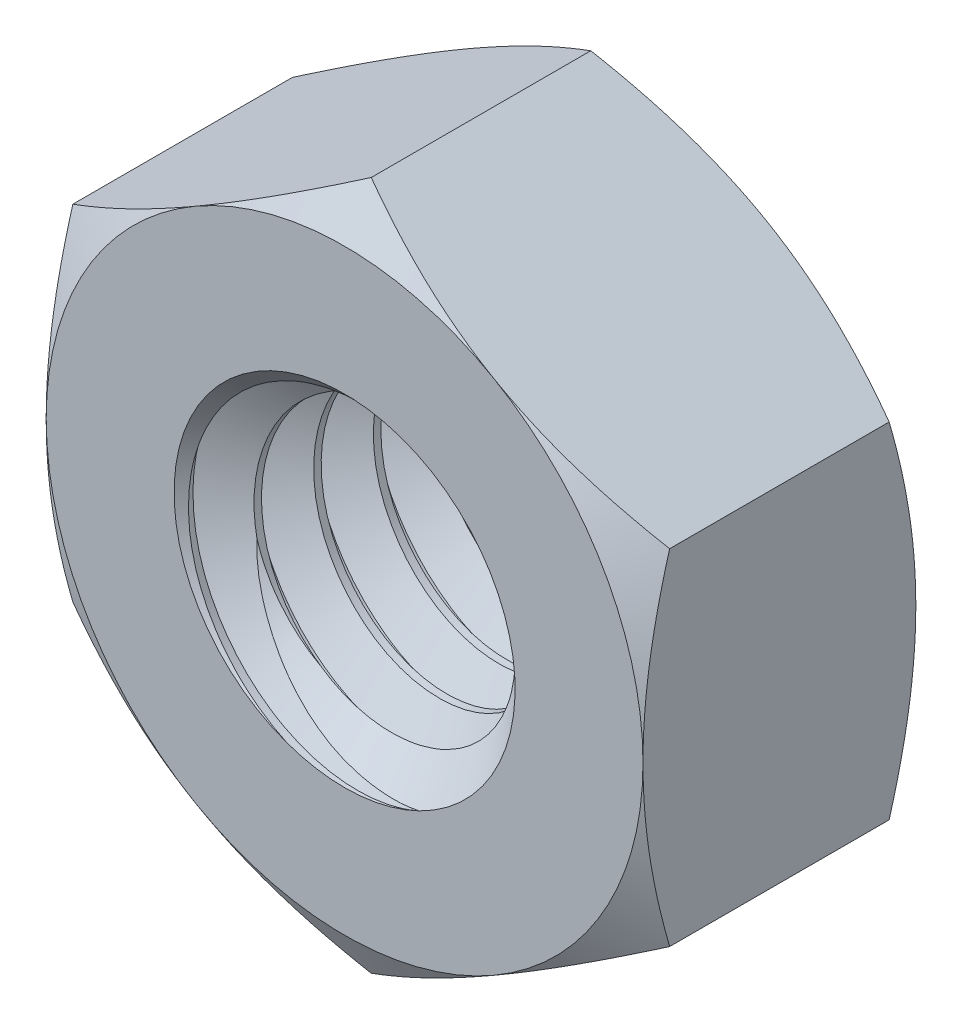
SolidWorks part; units mm, degrees
ref_plane "Front" through (0, 0, 0) normal (0, 0, 1) x (1, 0, 0)
ref_plane "Top" through (0, 0, 0) normal (0, 1, 0) x (1, 0, 0)
ref_plane "Right" through (0, 0, 0) normal (1, 0, 0) x (0, 0, -1)
sketch "Sketch1" plane through (0, 0, 0) normal (0, 0, 1) x (1, 0, 0)
  line L1 (-3.5, 2.0207) -> (-3.5, -2.0207)
  line L2 (-3.5, -2.0207) -> (0, -4.0415)
  line L3 (0, -4.0415) -> (3.5, -2.0207)
  line L4 (3.5, -2.0207) -> (3.5, 2.0207)
  line L5 (3.5, 2.0207) -> (0, 4.0415)
  line L6 (0, 4.0415) -> (-3.5, 2.0207)
  circle A0 centre (0, 0) radius 3.5 construction
  circle A1 centre (0, 0) radius 2 construction
  point P10 (0, 2)
  dimension "hex" = 7
  dimension "dia" = 4
extrude "Extrude1" add sketch "Sketch1" along normal mid plane 3.2
sketch "Sketch4" plane through (0, 0, -1.6) normal (0, 0, -1) x (-1, 0, 0)
  circle A0 centre (0, 0) radius 2 construction
  circle A1 centre (0, 0) radius 2
sketch "Sketch10" plane through (0, 0, 1.6) normal (0, 0, 1) x (1, 0, 0)
  circle A0 centre (0, 0) radius 2 construction
  circle A1 centre (0, 0) radius 2
extrude "Cut-Extrude2" cut sketch "Sketch10" against normal through all draft 45
sketch "Sketch11" plane through (0, 0, -1.6) normal (0, 0, -1) x (-1, 0, 0)
  circle A0 centre (0, 0) radius 2 construction
  circle A1 centre (0, 0) radius 2
extrude "Cut-Extrude3" cut sketch "Sketch11" against normal through all draft 45
sketch "Sketch13" plane through (0, 0, -1.6) normal (0, 0, -1) x (-1, 0, 0)
  circle A0 centre (0, 0) radius 2 construction
  circle A1 centre (0, 0) radius 2
extrude "Boss-Extrude1" add sketch "Sketch13" against normal up to vertex (3.2 mm away) separate body up to point (-3.5, 2.0207, 1.6)
curve "Helix/Spiral3" pitch 0.7 height 3.2 radius 2 centre (0, 0, -1.6) axis (0, 0, 1) start towards (0, 1, 0)
sketch "Sketch12" plane through (0, 0, 0) normal (1, 0, 0) x (0, 0, -1)
  line L0 (2.2125, 2) -> (1.6, 2)
  line L1 (2.2125, 2) -> (1.95, 1.5453)
  line L2 (1.95, 1.5453) -> (1.8625, 1.5453)
  line L3 (1.8625, 1.5453) -> (1.6, 2)
  line L4 (1.9062, 1.5453) -> (1.9062, 2) construction
  line L5 (1.7312, 1.7727) -> (2.0812, 1.7727) construction
  dimension "D1" = 60
  dimension "D2" = 0.0875
  dimension "D3" = 0.35
sweep "Cut-Sweep1" cut profiles "Sketch12" path "Helix/Spiral3" align with end faces yes
combine bodies "Combine1" operation type subtract main body 116 bodies to subtract 118
sketch "Sketch7" plane through (0, 0, 1.6) normal (0, 0, 1) x (1, 0, 0)
  circle A0 centre (0, 0) radius 3.5 construction
  circle A1 centre (0, 0) radius 3.5
extrude "Extrude2" cut sketch "Sketch7" against normal blind 25.4 draft 60 flip side to cut
mirror "Mirror2" about plane through (0, 0, 0) normal (0, 0, 1) of "Extrude2"
equation "\"D3@Helix/Spiral3\" = \"length@Extrude1\" "
equation "\"D2@Sketch12\" = \"D4@Helix/Spiral3\"*.125"
equation "\"D3@Sketch12\" = \"D4@Helix/Spiral3\"*.50"
